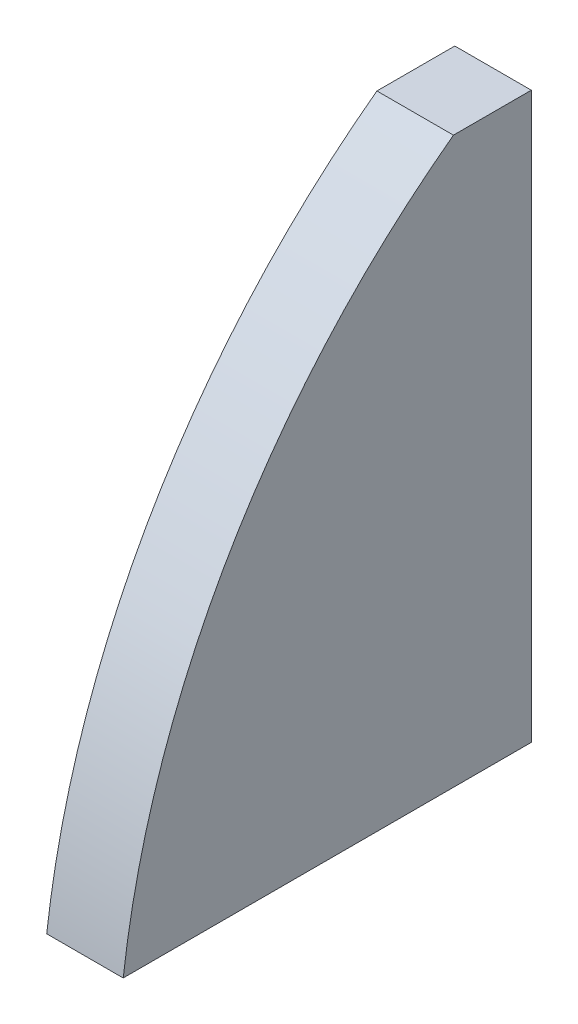
SolidWorks part; units mm, degrees
ref_plane "Спереди" through (0, 0, 0) normal (0, 0, 1) x (1, 0, 0)
ref_plane "Сверху" through (0, 0, 0) normal (0, 1, 0) x (1, 0, 0)
ref_plane "Справа" through (0, 0, 0) normal (1, 0, 0) x (0, 0, -1)
sketch "Эскиз1" plane through (0, 0, 0) normal (1, 0, 0) x (0, 0, -1)
  line L0 (-1612.6453, 200) -> (-812.6453, 200)
  line L1 (-812.6453, 200) -> (-812.6453, 1407.2074)
  arc A0 (-812.6453, 1407.2074) -> (-1612.6453, 200) centre (0, 0) ccw
  dimension "Радіус" = 1625
  dimension "Півширина кривошипа" = 200
  dimension "Ширина" = 800
extrude "Бобышка-Вытянуть1" add sketch "Эскиз1" along normal blind 150
chamfer "Фаска1" distance 100 angle 90 1 edges at (75, 1407.2074, 812.6453) first distance on face at (75, 803.6037, 812.6453)
equation "\"Радіус@Эскиз1\" = 1625"
equation "\"Півширина кривошипа@Эскиз1\" = 200"
equation "\"Ширина@Эскиз1\" = 800"
equation "\"Товщина@Бобышка-Вытянуть1\" = 150"
